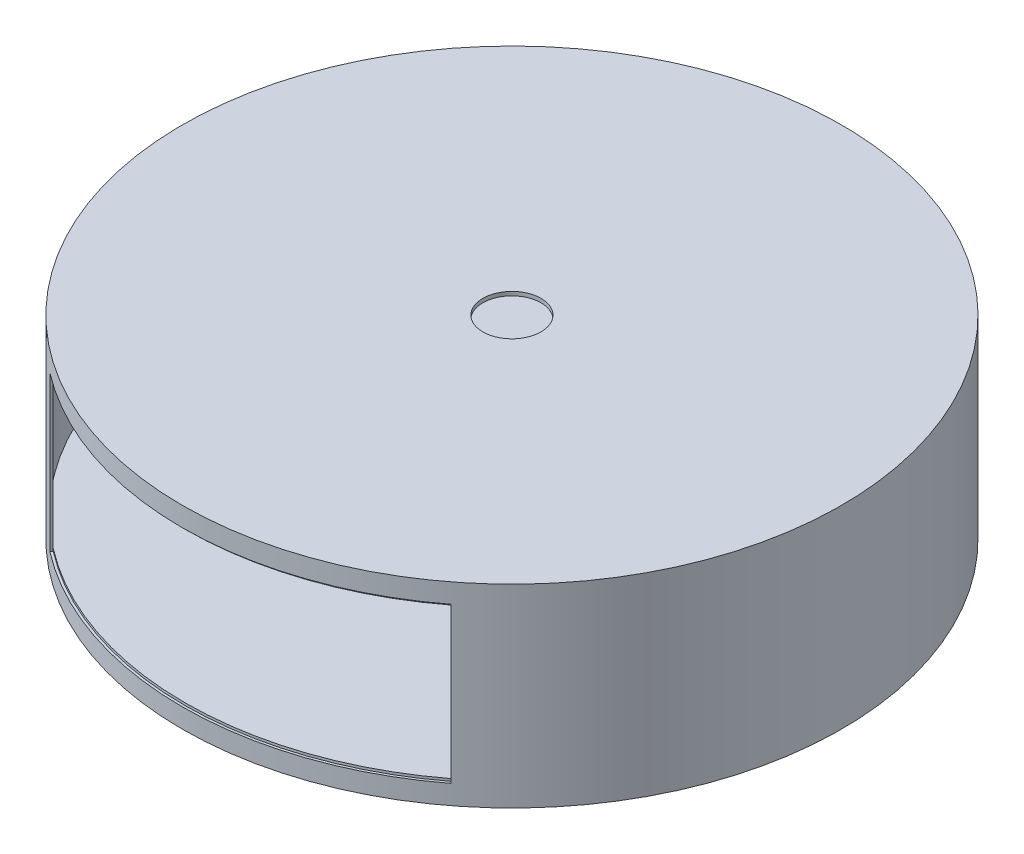
SolidWorks part; units mm, degrees
ref_plane "Front Plane" through (0, 0, 0) normal (0, 0, 1) x (1, 0, 0)
ref_plane "Top Plane" through (0, 0, 0) normal (0, 1, 0) x (1, 0, 0)
ref_plane "Right Plane" through (0, 0, 0) normal (1, 0, 0) x (0, 0, -1)
sketch "Sketch1" plane through (0, 0, 0) normal (0, 1, 0) x (1, 0, 0)
  circle A0 centre (0, 0) radius 215.9
  dimension "D1" = 431.8
extrude "Boss-Extrude1" add sketch "Sketch1" along normal mid plane 127 contours A0
sketch "Sketch2" plane through (0, 0, 0) normal (0, 1, 0) x (1, 0, 0)
  circle A0 centre (0, 0) radius 214.3125
  dimension "D1" = 428.625
extrude "Cut-Extrude1" cut sketch "Sketch2" against normal mid plane 98.425
sketch "Sketch3" plane through (0, 0, 0) normal (1, 0, 0) x (0, 0, -1)
  line L0 (-215.9, 50.8) -> (-215.9, -50.8)
  line L1 (-215.9, 63.5) -> (-215.9, -63.5) construction
  line L2 (-215.9, -50.8) -> (-214.3125, -50.8)
  line L3 (-214.3125, 49.2125) -> (-214.3125, -49.2125) construction
  line L4 (-214.3125, -50.8) -> (-214.3125, 50.8)
  line L5 (-214.3125, 50.8) -> (-215.9, 50.8)
  line L6 (215.9, 63.5) -> (-215.9, 63.5) construction
  line L7 (-215.9, -63.5) -> (215.9, -63.5) construction
  line L8 (0, 0) -> (0, 63.5) construction
  dimension "D1" = 12.7
  dimension "D2" = 12.7
revolve "Cut-Revolve1" cut sketch "Sketch3" angle 75 mid plane about L8
sketch "Sketch4" plane through (0, 63.5, 0) normal (0, 1, 0) x (1, 0, 0)
  circle A0 centre (0, 0) radius 19.05
  dimension "D1" = 38.1
extrude "Cut-Extrude2" cut sketch "Sketch4" against normal blind 2.54
equation "\"D2@Sketch3\"=\"D1@Sketch3\""
